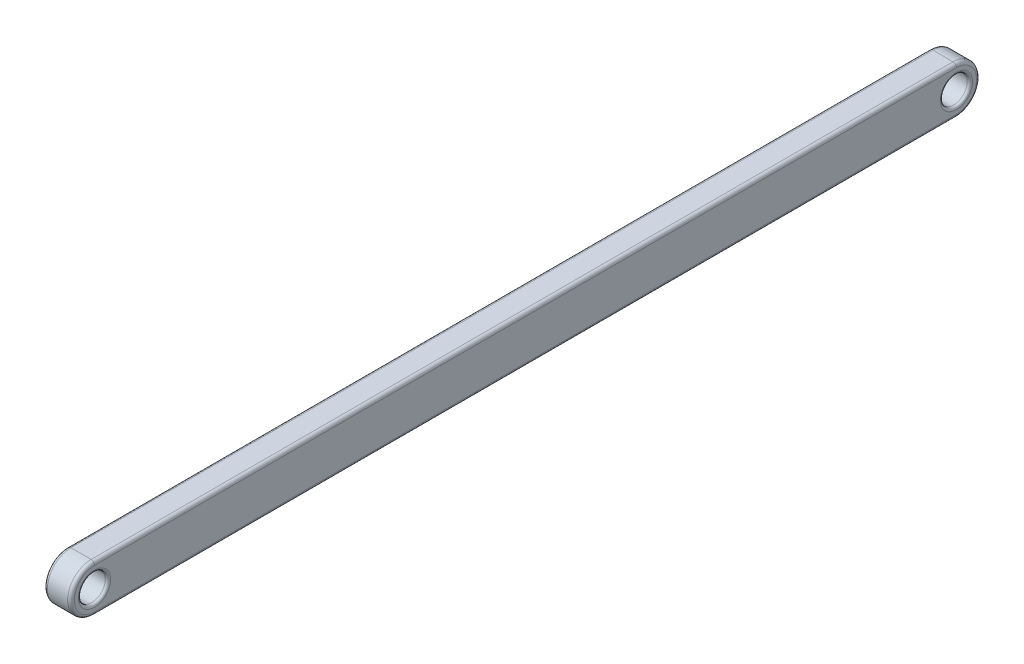
SolidWorks part; units mm, degrees
ref_plane "Front Plane" through (0, 0, 0) normal (0, 0, 1) x (1, 0, 0)
ref_plane "Top Plane" through (0, 0, 0) normal (0, 1, 0) x (1, 0, 0)
ref_plane "Right Plane" through (0, 0, 0) normal (1, 0, 0) x (0, 0, -1)
sketch "Sketch1" plane through (0, 0, 0) normal (1, 0, 0) x (0, 0, -1)
  line L1 (0, 0) -> (30, 0)
  line L2 (0, 0) -> (0, -1.75) construction
  line L3 (0, -1.75) -> (30, -1.75)
  line L4 (30, 0) -> (30, -1.75) construction
  line L5 (0, 0) -> (-1, 0)
  line L6 (0, 0) -> (0, -1.75) construction
  line L7 (0, -1.75) -> (-1, -1.75)
  line L8 (-1, 0) -> (-1, -1.75) construction
  line L9 (30, 0) -> (31, 0)
  line L10 (30, 0) -> (30, -1.75) construction
  line L11 (30, -1.75) -> (31, -1.75)
  line L12 (31, 0) -> (31, -1.75) construction
  line L16 (0, -0.875) -> (-1, -0.875) construction
  line L17 (30, -0.875) -> (31, -0.875) construction
  circle A0 centre (-1, -0.875) radius 0.5
  arc A1 (-1, -1.75) -> (-1, 0) centre (-1, -0.875) cw
  circle A2 centre (31, -0.875) radius 0.5
  arc A3 (31, 0) -> (31, -1.75) centre (31, -0.875) cw
  dimension "D1" = 1
  dimension "D4" = 1
  dimension "D2" = 1.75
  dimension "D3" = 1.75
  dimension "D5" = 32
  dimension "D6" = 1.75
  dimension "D7" = 1
  dimension "D8" = 1
extrude "Boss-Extrude1" add sketch "Sketch1" along normal blind 1 contours A3 L9 L1 L5 A1 L7 L3 L11 A2 A0 region at (0, -0.875, -15)
fillet "Fillet1" radius 0.125 8 edges at (1, -0.875, -31.875) (1, 0, -15) (1, -0.875, 1.875) (0, -0.875, -31.875) (0, 0, -15) (0, -0.875, 1.875) (1, -1.75, -15) (0, -1.75, -15)
fillet "Fillet2" radius 0.1 4 edges at (0, -0.875, -31.5) (1, -0.875, -31.5) (0, -0.875, 0.5) (1, -0.875, 0.5)
